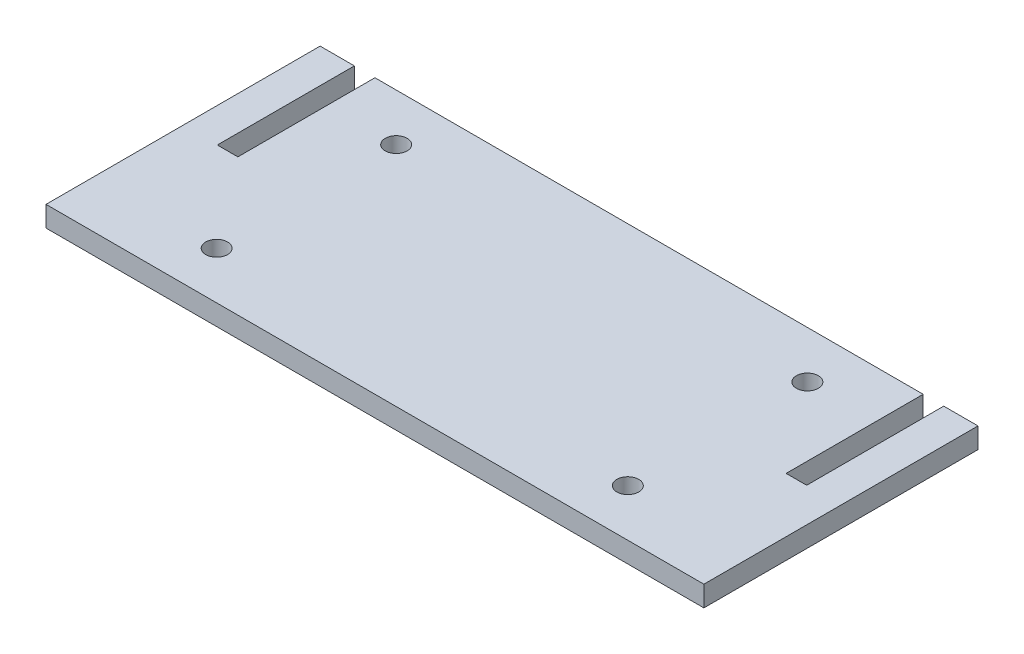
SolidWorks part; units mm, degrees
material "Acrylic (Medium-high impact)"
ref_plane "Front Plane" through (0, 0, 0) normal (0, 0, 1) x (1, 0, 0)
ref_plane "Top Plane" through (0, 0, 0) normal (0, 1, 0) x (1, 0, 0)
ref_plane "Right Plane" through (0, 0, 0) normal (1, 0, 0) x (0, 0, -1)
sketch "Sketch1" plane through (0, 0, 0) normal (0, 1, 0) x (1, 0, 0)
  line L0 (-30, 13.1) -> (30, -13.1) construction
  line L1 (-48, -20) -> (48, -20)
  line L2 (-48, -20) -> (-48, 20)
  line L3 (-48, 20) -> (-43, 20)
  line L4 (48, -20) -> (48, 20)
  line L5 (-48, -20) -> (48, 20) construction
  line L6 (-48, 20) -> (48, -20) construction
  line L7 (-30, 13.1) -> (-30, -13.1) construction
  line L8 (-30, -13.1) -> (30, -13.1) construction
  line L9 (30, -13.1) -> (30, 13.1) construction
  line L10 (-30, 13.1) -> (30, 13.1) construction
  line L11 (30, 13.1) -> (-30, -13.1) construction
  line L12 (-43, 20) -> (-43, 0)
  line L13 (-43, 0) -> (-40, 0)
  line L14 (-40, 0) -> (-40, 20)
  line L15 (40, 20) -> (40, 0)
  line L16 (40, 0) -> (43, 0)
  line L17 (43, 0) -> (43, 20)
  line L18 (-40, 20) -> (40, 20)
  line L19 (43, 20) -> (48, 20)
  circle A0 centre (-30, 13.1) radius 1.6
  circle A1 centre (30, 13.1) radius 1.6
  circle A2 centre (30, -13.1) radius 1.6
  circle A3 centre (-30, -13.1) radius 1.6
  point P0 (0, 0)
  dimension "D5" = 3.2
  dimension "D1" = 5
  dimension "D2" = 40
  dimension "D6" = 60
  dimension "D7" = 26.2
  dimension "D8" = 80
  dimension "D9" = 3
  dimension "D3" = 2
  dimension "D4" = 2
extrude "Boss-Extrude1" add sketch "Sketch1" along normal blind 3
